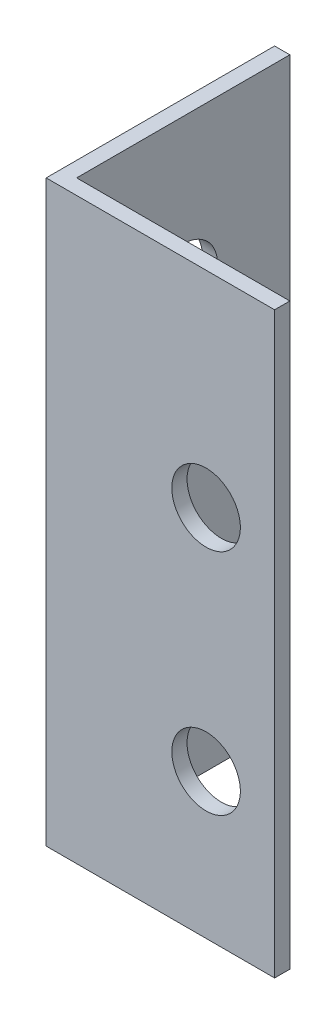
SolidWorks part; units mm, degrees
material "1060 Сплав"
ref_plane "Спереди" through (0, 0, 0) normal (0, 0, 1) x (1, 0, 0)
ref_plane "Сверху" through (0, 0, 0) normal (0, 1, 0) x (1, 0, 0)
ref_plane "Справа" through (0, 0, 0) normal (1, 0, 0) x (0, 0, -1)
sketch "Эскиз1" plane through (0, 0, 0) normal (0, 1, 0) x (1, 0, 0)
  line L0 (0, 0) -> (0, 15)
  line L1 (0, 15) -> (1, 15)
  line L2 (1, 15) -> (1, 1)
  line L3 (1, 1) -> (15, 1)
  line L4 (15, 1) -> (15, 0)
  line L5 (15, 0) -> (0, 0)
  dimension "D1" = 1
  dimension "D2" = 15
extrude "Бобышка-Вытянуть1" add sketch "Эскиз1" along normal blind 38
sketch "Эскиз2" plane through (0, 0, -1) normal (0, 0, -1) x (-1, 0, 0)
  circle A0 centre (-10.5, 9.5) radius 2.25 construction
  circle A1 centre (-10.5, 9.5) radius 2.25
extrude "Вырез-Вытянуть1" cut sketch "Эскиз2" against normal through all
sketch "Эскиз3" plane through (0, 0, -1) normal (0, 0, -1) x (-1, 0, 0)
  line L0 (0, 38) -> (0, 0) construction
  line L1 (0, 38) -> (-15, 38) construction
  circle A1 centre (-10.5, 24.5) radius 2.25
  dimension "D1" = 10.5
  dimension "D2" = 13.5
  dimension "D3" = 4.5
extrude "Вырез-Вытянуть2" cut sketch "Эскиз3" against normal through all
sketch "Эскиз4" plane through (1, 0, 0) normal (1, 0, 0) x (0, 0, -1)
  line L0 (8, 38) -> (8, 28.5) construction
  line L1 (1, 38) -> (15, 38) construction
  circle A0 centre (8, 28.5) radius 2.25
  dimension "D2" = 4.5
  dimension "D1" = 9.5
extrude "Вырез-Вытянуть3" cut sketch "Эскиз4" against normal through all
sketch "Эскиз5" plane through (1, 0, 0) normal (1, 0, 0) x (0, 0, -1)
  line L0 (8, 0) -> (8, 9.5) construction
  line L1 (1, 0) -> (15, 0) construction
  circle A0 centre (8, 9.5) radius 2.25
  dimension "D1" = 4.5
  dimension "D2" = 9.5
extrude "Вырез-Вытянуть4" cut sketch "Эскиз5" against normal through all
